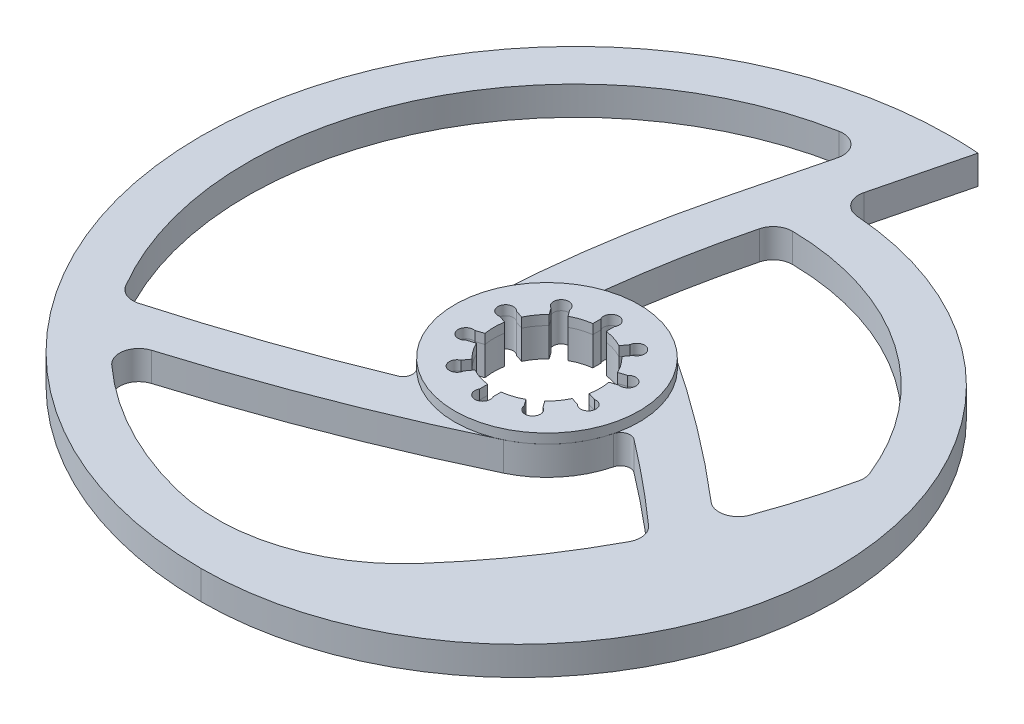
SolidWorks part; units mm, degrees
material "AISI Type A2 Tool Steel"
ref_plane "Front Plane" through (0, 0, 0) normal (0, 0, 1) x (1, 0, 0)
ref_plane "Top Plane" through (0, 0, 0) normal (0, 1, 0) x (1, 0, 0)
ref_plane "Right Plane" through (0, 0, 0) normal (1, 0, 0) x (0, 0, -1)
other "Center of Mass"
other "Bounding Box"
ref_plane "Default Plane" through (0, 2.286, 19.05) normal (0, -1, 0) x (-1, 0, 0)
sketch "Sketch1" plane through (0, 0, 0) normal (0, 1, 0) x (1, 0, 0)
  circle A0 centre (0, 0) radius 133.35 construction
  circle A1 centre (0, 0) radius 30.48
  circle A2 centre (0, 0) radius 17.4625
  dimension "D1" = 266.7
  dimension "D2" = 60.96
  dimension "D3" = 34.925
extrude "Boss-Extrude1" add sketch "Sketch1" along normal mid plane 9.525
sketch "Sketch5" plane through (0, 4.7625, 0) normal (0, 1, 0) x (1, 0, 0)
  line L0 (0, 17.4625) -> (0, 21.2725) construction
  line L2 (-2.2225, 17.3205) -> (2.2225, 17.3205)
  line L3 (-2.2225, 17.3205) -> (-2.2225, 20.0168)
  line L5 (2.2225, 17.3205) -> (2.2225, 20.0168)
  arc A0 (2.2225, 20.0168) -> (-2.2225, 20.0168) centre (0, 21.2725) ccw
  circle A1 centre (0, 0) radius 17.4625 construction
  circle A2 centre (0, 21.2725) radius 4.5847 construction
  dimension "D2" = 5.1054
  dimension "D4" = 9.1694
  dimension "D1" = 3.81
  dimension "D3" = 4.445
extrude "Cut-Extrude2" cut sketch "Sketch5" against normal through all
pattern_circular "CirPattern1" count 10 over 360 about axis through (0, 4.7625, 0) along (0, -1, 0) of "Cut-Extrude2"
sketch "Sketch6" plane through (0, 4.7625, 0) normal (0, 1, 0) x (1, 0, 0)
  circle A0 centre (0, 0) radius 17.526
  circle A1 centre (0, 0) radius 17.4625 construction
  dimension "D1" = 0.0635
extrude "Cut-Extrude3" cut sketch "Sketch6" against normal through all
sketch "Sketch11" plane through (0, 4.7625, 0) normal (0, 1, 0) x (1, 0, 0)
  line L20 (2.2225, -20.0168) -> (2.2225, -17.3845)
  line L21 (-2.2225, -17.3845) -> (-2.2225, -20.0168)
  line L22 (-9.9675, -17.5003) -> (-8.4203, -15.3707)
  line L23 (-12.0164, -12.758) -> (-13.5636, -14.8876)
  line L24 (-18.3503, -8.2993) -> (-15.8469, -7.4858)
  line L25 (-17.2204, -3.2584) -> (-19.7239, -4.0718)
  line L26 (-19.7239, 4.0718) -> (-17.2204, 3.2584)
  line L27 (-15.8469, 7.4858) -> (-18.3503, 8.2993)
  line L28 (-13.5636, 14.8876) -> (-12.0164, 12.758)
  line L29 (-8.4203, 15.3707) -> (-9.9675, 17.5003)
  line L30 (-2.2225, 20.0168) -> (-2.2225, 17.3845)
  line L31 (2.2225, 17.3845) -> (2.2225, 20.0168)
  line L32 (9.9675, 17.5003) -> (8.4203, 15.3707)
  line L33 (12.0164, 12.758) -> (13.5636, 14.8876)
  line L34 (18.3503, 8.2993) -> (15.8469, 7.4858)
  line L35 (17.2204, 3.2584) -> (19.7239, 4.0718)
  line L36 (19.7239, -4.0718) -> (17.2204, -3.2584)
  line L37 (15.8469, -7.4858) -> (18.3503, -8.2993)
  line L38 (13.5636, -14.8876) -> (12.0164, -12.758)
  line L39 (8.4203, -15.3707) -> (9.9675, -17.5003)
  line L40 (2.2225, -20.0168) -> (2.2225, -17.3845)
  line L41 (-2.2225, -17.3845) -> (-2.2225, -20.0168)
  line L42 (-9.9675, -17.5003) -> (-8.4203, -15.3707)
  line L43 (-12.0164, -12.758) -> (-13.5636, -14.8876)
  line L44 (-18.3503, -8.2993) -> (-15.8469, -7.4858)
  line L45 (-17.2204, -3.2584) -> (-19.7239, -4.0718)
  line L46 (-19.7239, 4.0718) -> (-17.2204, 3.2584)
  line L47 (-15.8469, 7.4858) -> (-18.3503, 8.2993)
  line L48 (-13.5636, 14.8876) -> (-12.0164, 12.758)
  line L49 (-8.4203, 15.3707) -> (-9.9675, 17.5003)
  line L50 (-2.2225, 20.0168) -> (-2.2225, 17.3845)
  line L51 (2.2225, 17.3845) -> (2.2225, 20.0168)
  line L52 (9.9675, 17.5003) -> (8.4203, 15.3707)
  line L53 (12.0164, 12.758) -> (13.5636, 14.8876)
  line L54 (18.3503, 8.2993) -> (15.8469, 7.4858)
  line L55 (17.2204, 3.2584) -> (19.7239, 4.0718)
  line L56 (19.7239, -4.0718) -> (17.2204, -3.2584)
  line L57 (15.8469, -7.4858) -> (18.3503, -8.2993)
  line L58 (13.5636, -14.8876) -> (12.0164, -12.758)
  line L59 (8.4203, -15.3707) -> (9.9675, -17.5003)
  circle A1 centre (0, 0) radius 30.48
  circle A2 centre (0, 0) radius 30.48
  arc A20 (2.2225, -17.3845) -> (8.4203, -15.3707) centre (0, 0) ccw
  arc A21 (-2.2225, -20.0168) -> (2.2225, -20.0168) centre (0, -21.2725) ccw
  arc A22 (-8.4203, -15.3707) -> (-2.2225, -17.3845) centre (0, 0) ccw
  arc A23 (-13.5636, -14.8876) -> (-9.9675, -17.5003) centre (-12.5037, -17.2098) ccw
  arc A24 (-15.8469, -7.4858) -> (-12.0164, -12.758) centre (0, 0) ccw
  arc A25 (-19.7239, -4.0718) -> (-18.3503, -8.2993) centre (-20.2313, -6.5736) ccw
  arc A26 (-17.2204, 3.2584) -> (-17.2204, -3.2584) centre (0, 0) ccw
  arc A27 (-18.3503, 8.2993) -> (-19.7239, 4.0718) centre (-20.2313, 6.5736) ccw
  arc A28 (-12.0164, 12.758) -> (-15.8469, 7.4858) centre (0, 0) ccw
  arc A29 (-9.9675, 17.5003) -> (-13.5636, 14.8876) centre (-12.5037, 17.2098) ccw
  arc A30 (-2.2225, 17.3845) -> (-8.4203, 15.3707) centre (0, 0) ccw
  arc A31 (2.2225, 20.0168) -> (-2.2225, 20.0168) centre (0, 21.2725) ccw
  arc A32 (8.4203, 15.3707) -> (2.2225, 17.3845) centre (0, 0) ccw
  arc A33 (13.5636, 14.8876) -> (9.9675, 17.5003) centre (12.5037, 17.2098) ccw
  arc A34 (15.8469, 7.4858) -> (12.0164, 12.758) centre (0, 0) ccw
  arc A35 (19.7239, 4.0718) -> (18.3503, 8.2993) centre (20.2313, 6.5736) ccw
  arc A36 (17.2204, -3.2584) -> (17.2204, 3.2584) centre (0, 0) ccw
  arc A37 (18.3503, -8.2993) -> (19.7239, -4.0718) centre (20.2313, -6.5736) ccw
  arc A38 (12.0164, -12.758) -> (15.8469, -7.4858) centre (0, 0) ccw
  arc A39 (9.9675, -17.5003) -> (13.5636, -14.8876) centre (12.5037, -17.2098) ccw
  arc A40 (2.2225, -17.3845) -> (8.4203, -15.3707) centre (0, 0) ccw
  arc A41 (-2.2225, -20.0168) -> (2.2225, -20.0168) centre (0, -21.2725) ccw
  arc A42 (-8.4203, -15.3707) -> (-2.2225, -17.3845) centre (0, 0) ccw
  arc A43 (-13.5636, -14.8876) -> (-9.9675, -17.5003) centre (-12.5037, -17.2098) ccw
  arc A44 (-15.8469, -7.4858) -> (-12.0164, -12.758) centre (0, 0) ccw
  arc A45 (-19.7239, -4.0718) -> (-18.3503, -8.2993) centre (-20.2313, -6.5736) ccw
  arc A46 (-17.2204, 3.2584) -> (-17.2204, -3.2584) centre (0, 0) ccw
  arc A47 (-18.3503, 8.2993) -> (-19.7239, 4.0718) centre (-20.2313, 6.5736) ccw
  arc A48 (-12.0164, 12.758) -> (-15.8469, 7.4858) centre (0, 0) ccw
  arc A49 (-9.9675, 17.5003) -> (-13.5636, 14.8876) centre (-12.5037, 17.2098) ccw
  arc A50 (-2.2225, 17.3845) -> (-8.4203, 15.3707) centre (0, 0) ccw
  arc A51 (2.2225, 20.0168) -> (-2.2225, 20.0168) centre (0, 21.2725) ccw
  arc A52 (8.4203, 15.3707) -> (2.2225, 17.3845) centre (0, 0) ccw
  arc A53 (13.5636, 14.8876) -> (9.9675, 17.5003) centre (12.5037, 17.2098) ccw
  arc A54 (15.8469, 7.4858) -> (12.0164, 12.758) centre (0, 0) ccw
  arc A55 (19.7239, 4.0718) -> (18.3503, 8.2993) centre (20.2313, 6.5736) ccw
  arc A56 (17.2204, -3.2584) -> (17.2204, 3.2584) centre (0, 0) ccw
  arc A57 (18.3503, -8.2993) -> (19.7239, -4.0718) centre (20.2313, -6.5736) ccw
  arc A58 (12.0164, -12.758) -> (15.8469, -7.4858) centre (0, 0) ccw
  arc A59 (9.9675, -17.5003) -> (13.5636, -14.8876) centre (12.5037, -17.2098) ccw
  dimension "D1" = 0
  dimension "D2" = 0
extrude "Boss-Extrude5" add sketch "Sketch11" along normal blind 3.175 separate body
sketch "Sketch2" plane through (0, 4.7625, 0) normal (0, 1, 0) x (1, 0, 0)
  line L4 (0, 133.35) -> (0, 0) construction
  line L5 (0, 0) -> (0, -133.35) construction
  line L6 (-9.4646, -133.0137) -> (0, 0) construction
  line L7 (0, 0) -> (9.4646, 133.0137) construction
  line L8 (0, 95.25) -> (9.4646, 133.0137)
  line L10 (0, -95.25) -> (0, -114.3) construction
  line L11 (0, -133.35) -> (0, -114.3) construction
  line L12 (-20.1039, 77.7238) -> (-10.1, 117.6393)
  circle A0 centre (0, 0) radius 133.35 construction
  circle A1 centre (0, 0) radius 133.35 construction
  arc A2 (0, 133.35) -> (9.4646, 133.0137) centre (0, 0) cw
  arc A5 (0, -114.3) -> (0, 95.25) centre (0, -9.525) ccw
  arc A9 (0, 133.35) -> (0, -114.3) centre (0, 9.525) ccw
  circle A15 centre (0, 0) radius 95.25 construction
  arc A16 (-10.1, 117.6393) -> (-10.1, 117.6393) centre (-10.1, 117.6393) cw
  arc A17 (-10.1, 117.6393) -> (0, -99.06) centre (0, 9.525) ccw
  arc A18 (0, -99.06) -> (-20.1039, 77.7238) centre (0, -9.525) ccw
  dimension "D2" = 38.1
  dimension "D3" = 15.24
  dimension "D1" = 10
extrude "Boss-Extrude2" add sketch "Sketch2" against normal through all
sketch "Sketch9" plane through (0, 4.7625, 0) normal (0, 1, 0) x (1, 0, 0)
  line L1 (0, 95.25) -> (9.4646, 133.0137) construction
  line L2 (-68.2895, -114.5372) -> (-6.1986, 133.2059) construction
  line L3 (-112.2603, -71.9711) -> (133.3369, -1.8719) construction
  line L4 (118.459, -61.2348) -> (-65.0473, 116.4091) construction
  line L5 (-112.2603, -71.9711) -> (-68.2895, -114.5372) construction
  line L6 (118.459, -61.2348) -> (133.3369, -1.8719) construction
  line L7 (-65.0473, 116.4091) -> (-6.1986, 133.2059) construction
  line L8 (-28.7073, 28.8716) -> (-13.5482, 27.3034) construction
  line L9 (-17.8522, -24.7048) -> (-11.9329, -38.7483) construction
  line L10 (30.3658, -2.636) -> (39.4535, 9.598) construction
  line L11 (-20.1039, 77.7238) -> (-10.1, 117.6393) construction
  arc A0 (-30.4727, 0.6691) -> (-20.1039, 77.7238) centre (317.8601, -6.9789) cw
  circle A1 centre (0, 0) radius 30.48 construction
  arc A4 (-3.7818, 79.9301) -> (-20.1039, 77.7238) centre (0, -9.525) ccw
  arc A5 (-13.5482, 27.3034) -> (-3.7818, 79.9301) centre (317.8601, -6.9789) cw
  circle A7 centre (0, 0) radius 133.35 construction
  arc A8 (-80.8168, -62.9964) -> (13.1009, -27.5208) centre (-246.737, 518.3163) ccw
  arc A9 (81.4534, -46.6985) -> (86.98, -30.7615) centre (0, -9.525) ccw
  circle A10 centre (0, 0) radius 30.48 construction
  arc A11 (-90.8326, -49.9741) -> (-17.8522, -24.7048) centre (-246.737, 518.3163) ccw
  arc A13 (86.98, -30.7615) -> (16.7293, 25.4786) centre (-246.1494, -374.8845) ccw
  arc A16 (30.3658, -2.636) -> (81.4534, -46.6985) centre (-246.1494, -374.8845) cw
  arc A17 (0, -99.06) -> (-20.1039, 77.7238) centre (0, -9.525) ccw construction
  arc A18 (-10.1, 117.6393) -> (0, -99.06) centre (0, 9.525) ccw construction
  arc A19 (-17.8522, -24.7048) -> (13.1009, -27.5208) centre (0, 0) ccw
  arc A20 (-90.8326, -49.9741) -> (-80.8168, -62.9964) centre (0, 9.525) ccw
  arc A21 (30.3658, -2.636) -> (16.7293, 25.4786) centre (0, 0) ccw
  arc A22 (-13.5482, 27.3034) -> (-30.4727, 0.6691) centre (0, 0) ccw
  point P3 (-12.4746, 27.8103)
extrude "Boss-Extrude3" add sketch "Sketch9" against normal up to surface (9.525 mm away) up to face at (-11.5359, -4.7625, -34.2476)
sketch "Sketch10" plane through (0, 4.7625, 0) normal (0, 1, 0) x (1, 0, 0)
  line L0 (-26.8153, -95.6969) -> (0, 0) construction
  line L1 (0, 0) -> (34.7016, -76.6893) construction
  line L2 (65.371, -31.3955) -> (0, 0) construction
  line L3 (0, 0) -> (83.9943, 21.4826) construction
  arc A2 (81.4534, -46.6985) -> (30.3658, -2.636) centre (-246.1494, -374.8845) ccw construction
  arc A3 (81.4534, -46.6985) -> (65.371, -31.3955) centre (-246.1494, -374.8845) ccw
  arc A6 (-26.8153, -95.6969) -> (34.7016, -76.6893) centre (-11.5854, -35.9357) ccw
  arc A7 (34.7016, -76.6893) -> (65.371, -31.3955) centre (-127.7448, 66.3371) ccw
  arc A8 (-80.8168, -62.9964) -> (0, -99.06) centre (0, 9.525) ccw construction
  arc A9 (0, -99.06) -> (81.4534, -46.6985) centre (0, -9.525) ccw
  arc A10 (0, -99.06) -> (-26.8153, -95.6969) centre (0, 9.525) cw
  arc A11 (0, -99.06) -> (81.4534, -46.6985) centre (0, -9.525) ccw construction
  arc A12 (86.98, -30.7615) -> (-3.7818, 79.9301) centre (0, -9.525) ccw construction
  arc A13 (86.98, -30.7615) -> (16.7293, 25.4786) centre (-246.1494, -374.8845) ccw construction
  arc A14 (86.98, -30.7615) -> (83.9943, 21.4826) centre (0, -9.525) ccw
  arc A15 (86.98, -30.7615) -> (72.0448, -16.9064) centre (-246.1494, -374.8845) ccw
  arc A16 (72.0448, -16.9064) -> (83.9943, 21.4826) centre (-127.7448, 66.3371) ccw
  point P5 (32.1462, -68.1523)
  dimension "D1" = 22.1996
  dimension "D2" = 40
  dimension "D3" = 40
  dimension "D4" = 40
extrude "Boss-Extrude4" add sketch "Sketch10" against normal up to surface (9.525 mm away) up to face at (-44.3187, -4.7625, -28.3406)
fillet "Fillet1" radius 6.35 7 edges at (65.371, 0, 31.3955) (72.0448, 0, 16.9064) (83.9943, 0, -21.4826) (-90.8326, 0, 49.9741) (-3.7818, 0, -79.9301) (-10.1, 0, -117.6393) (-80.8168, 0, 62.9964)
fillet "Fillet2" radius 3.175 3 edges at (-13.5482, 0, -27.3034) (30.3658, 0, 2.636) (-17.8522, 0, 24.7048)
fillet "Fillet3" radius 6.35 1 edges at (0, 0, -95.25)
equation "\"Unit Measure\"= \"BoundingVolume\" / \"Thickness\"'in^2"
